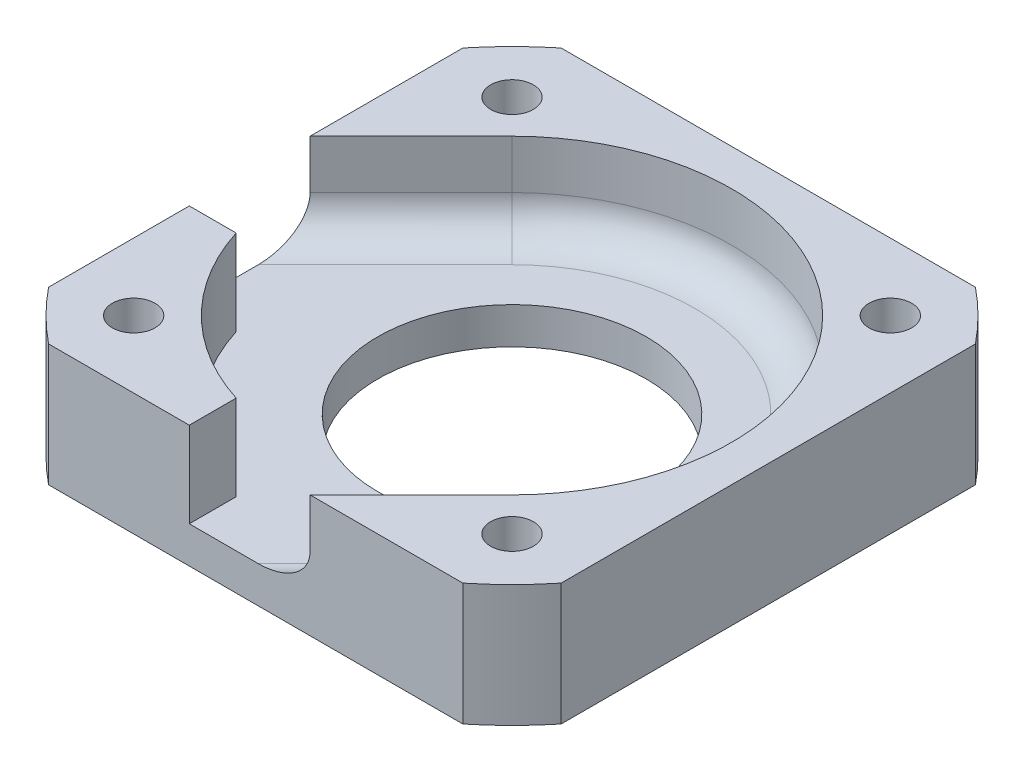
SolidWorks part; units mm, degrees
ref_plane "Front Plane" through (0, 0, 0) normal (0, 0, 1) x (1, 0, 0)
ref_plane "Top Plane" through (0, 0, 0) normal (0, 1, 0) x (1, 0, 0)
ref_plane "Right Plane" through (0, 0, 0) normal (1, 0, 0) x (0, 0, -1)
sketch "Sketch2" plane through (0, 0, 0) normal (0, 1, 0) x (1, 0, 0)
  line L1 (-21, 21) -> (21, 21)
  line L2 (-21, 21) -> (-21, -21)
  line L3 (-21, -21) -> (21, -21)
  line L4 (21, 21) -> (21, -21)
  line L5 (-21, 21) -> (21, -21) construction
  line L6 (-21, -21) -> (21, 21) construction
  point P0 (0, 0)
  dimension "D1" = 42
extrude "Boss-Extrude1" add sketch "Sketch2" along normal blind 10
sketch "Sketch3" plane through (0, 10, 0) normal (0, 1, 0) x (1, 0, 0)
  circle A0 centre (0, 0) radius 11
  dimension "D1" = 22
extrude "Cut-Extrude1" cut sketch "Sketch3" against normal through all
sketch "Sketch4" plane through (0, 10, 0) normal (0, 1, 0) x (1, 0, 0)
  line L1 (-15.5, 15.5) -> (15.5, 15.5) construction
  line L2 (-15.5, 15.5) -> (-15.5, -15.5) construction
  line L3 (-15.5, -15.5) -> (15.5, -15.5) construction
  line L4 (15.5, 15.5) -> (15.5, -15.5) construction
  line L5 (-15.5, 15.5) -> (15.5, -15.5) construction
  line L6 (-15.5, -15.5) -> (15.5, 15.5) construction
  circle A0 centre (-15.5, 15.5) radius 1.75
  circle A1 centre (15.5, 15.5) radius 1.75
  circle A2 centre (15.5, -15.5) radius 1.75
  circle A3 centre (-15.5, -15.5) radius 1.75
  point P0 (0, 0)
  point P6 (0, 0)
  point P16 (0, 0)
  dimension "D3" = 3.5
  dimension "D1" = 31
  dimension "D2" = 31
  dimension "D4" = 4
extrude "Cut-Extrude2" cut sketch "Sketch4" against normal through all
sketch "Sketch5" plane through (0, 10, 0) normal (0, 1, 0) x (1, 0, 0)
  circle A0 centre (0, 0) radius 27
  circle A1 centre (0, 0) radius 29.6985
  dimension "D1" = 54
extrude "Cut-Extrude4" cut sketch "Sketch5" against normal through all
sketch "Sketch6" plane through (0, 10, 0) normal (0, 1, 0) x (1, 0, 0)
  line L0 (-21, 4.4558) -> (-12.7279, 12.7279)
  line L1 (12.7279, -12.7279) -> (4.4558, -21)
  line L9 (-21, 16.9706) -> (-21, -16.9706) construction
  line L10 (-16.9706, -21) -> (16.9706, -21) construction
  line L11 (-7.7782, 7.7782) -> (-21, -5.4437) construction
  line L12 (4.4558, 21) -> (21, 4.4558) construction
  line L13 (7.5251, 21) -> (21, 7.5251) construction
  line L14 (16.9706, 21) -> (-16.9706, 21) construction
  line L15 (21, -16.9706) -> (21, 16.9706) construction
  line L18 (7.7782, -7.7782) -> (-5.4437, -21) construction
  line L19 (-21, 4.4558) -> (-21, -5.4437)
  line L21 (-5.4437, -17.1571) -> (-5.4437, -21)
  line L22 (-5.4437, -21) -> (4.4558, -21)
  line L23 (-17.1571, -5.4437) -> (-21, -5.4437)
  arc A0 (-12.7279, 12.7279) -> (12.7279, -12.7279) centre (0, 0) cw
  circle A2 centre (0, 0) radius 11 construction
  arc A4 (-12.7279, 12.7279) -> (12.7279, -12.7279) centre (0, 0) ccw construction
  circle A5 centre (15.5, 15.5) radius 1.75 construction
  arc A6 (-17.1571, -5.4437) -> (-5.4437, -17.1571) centre (0, 0) ccw
  point P25 (-5.8789, -21)
  point P28 (-21, -6.9457)
  point P33 (-21, -5.7894)
  dimension "D1" = 45
  dimension "D3" = 18
  dimension "D2" = 45
  dimension "D4" = 45
extrude "Cut-Extrude5" cut sketch "Sketch6" against normal offset from surface (7 mm away) 3 up to face at (-15.5, 0, 17.25)
fillet "Fillet1" radius 3 3 edges at (-16.864, 3, -8.5919) (8.5919, 3, 16.864) (12.7279, 3, -12.7279)
